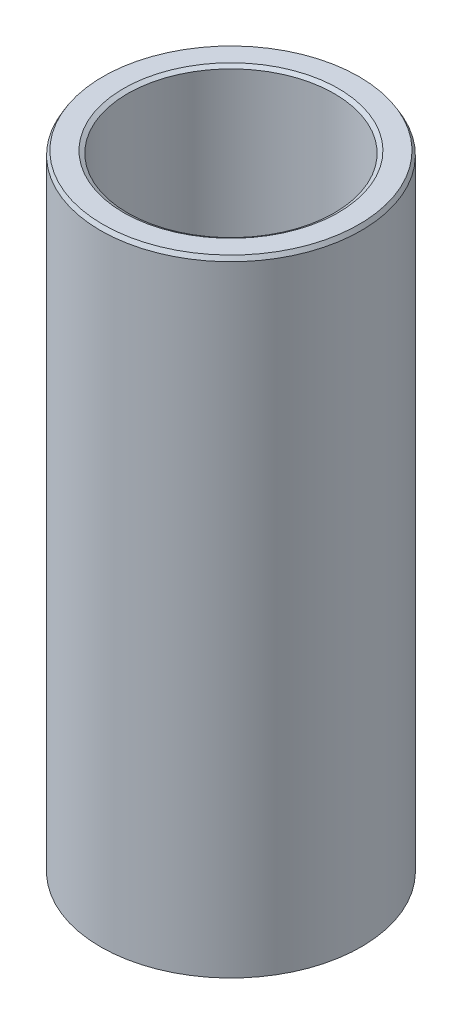
SolidWorks part; units mm, degrees
ref_plane "Front Plane" through (0, 0, 0) normal (0, 0, 1) x (1, 0, 0)
ref_plane "Top Plane" through (0, 0, 0) normal (0, 1, 0) x (1, 0, 0)
ref_plane "Right Plane" through (0, 0, 0) normal (1, 0, 0) x (0, 0, -1)
sketch "Sketch1" plane through (0, 0, 0) normal (0, 1, 0) x (1, 0, 0)
  circle A0 centre (0, 0) radius 40
  dimension "SLEEVE_OD" = 80
extrude "Boss-Extrude1" add sketch "Sketch1" along normal blind 192.239
sketch "Sketch2" plane through (0, 0, 0) normal (0, 1, 0) x (1, 0, 0)
  circle A0 centre (0, 0) radius 31.7063
  dimension "BORE_D" = 63.4125
extrude "Cut-Extrude1" cut sketch "Sketch2" along normal through all
chamfer "Chamfer1" distance 1.2578 angle 30 4 edges at (0, 192.239, 31.7063) (0, 0, 31.7063) (0, 0, 40) (0, 192.239, 40) first distance on face at (0, 192.239, 31.7063) first distance on face at (0, 0, 31.7063) first distance on face at (0, 192.239, 40)
